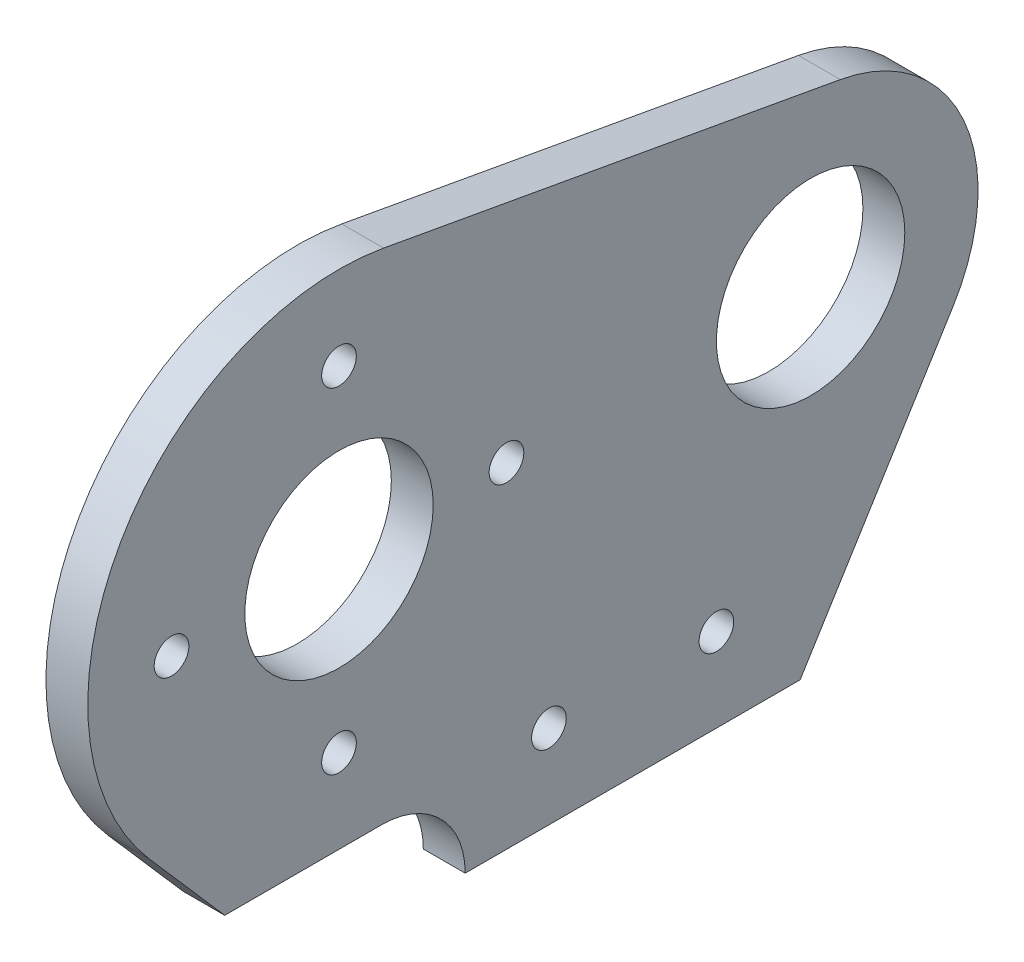
SolidWorks part; units mm, degrees
material "6061-T6 (SS)"
ref_plane "Front Plane" through (0, 0, 0) normal (0, 0, 1) x (1, 0, 0)
ref_plane "Top Plane" through (0, 0, 0) normal (0, 1, 0) x (1, 0, 0)
ref_plane "Right Plane" through (0, 0, 0) normal (1, 0, 0) x (0, 0, -1)
sketch "Sketch1" plane through (0, 0, 0) normal (1, 0, 0) x (0, 0, -1)
  line L0 (25.4, 12.7) -> (38.1, 12.7) construction
  line L1 (0, 0) -> (76.2, 0)
  line L5 (38.1, 12.7) -> (63.5, 12.7) construction
  line L6 (63.5, 12.7) -> (77.7875, 12.7) construction
  line L7 (77.7875, 12.7) -> (77.7875, 50.8) construction
  line L8 (77.7875, 50.8) -> (17.2031, 50.8) construction
  line L9 (76.2, 0) -> (99.3809, 37.4252)
  line L12 (6.2611, 50.8) -> (6.2611, 76.2) construction
  line L13 (0, 0) -> (-22.459, 25.7648)
  line L15 (38.1, 12.7) -> (38.1, 39.0177) construction
  line L18 (6.2611, 50.8) -> (6.2611, 25.4) construction
  line L19 (6.2611, 50.8) -> (31.6611, 50.8) construction
  line L20 (6.2611, 50.8) -> (-19.1389, 50.8) construction
  line L21 (82.2974, 75.7964) -> (13.026, 88.2946)
  line L22 (77.7875, 50.8) -> (6.2611, 50.8) construction
  circle A0 centre (38.1, 12.7) radius 2.6289
  circle A1 centre (63.5, 12.7) radius 2.6289
  circle A2 centre (77.7875, 50.8) radius 14.2875
  arc A3 (99.3809, 37.4252) -> (82.2974, 75.7964) centre (77.7875, 50.8) ccw
  circle A4 centre (6.2611, 50.8) radius 14.2875
  circle A5 centre (6.2611, 76.2) radius 2.6289
  arc A9 (13.026, 88.2946) -> (-22.459, 25.7648) centre (6.2611, 50.8) ccw
  circle A10 centre (6.2611, 25.4) radius 2.6289
  circle A11 centre (31.6611, 50.8) radius 2.6289
  circle A12 centre (-19.1389, 50.8) radius 2.6289
  dimension "D5" = 5.2578
  dimension "D6" = 5.2578
  dimension "D9" = 28.575
  dimension "D10" = 50.8
  dimension "D11" = 28.575
  dimension "D13" = 5.2578
  dimension "D15" = 76.2
  dimension "D17" = 5.2578
  dimension "D19" = 5.2578
  dimension "D21" = 5.2578
  dimension "D2" = 76.2
  dimension "D3" = 12.7
  dimension "D4" = 25.4
  dimension "D7" = 14.2875
  dimension "D8" = 38.1
  dimension "D12" = 25.4
  dimension "D16" = 71.5264
  dimension "D14" = 25.4
  dimension "D18" = 25.4
  dimension "D20" = 25.4
  dimension "D22" = 12.7
  dimension "D23" = 12.7
extrude "Boss-Extrude1" add sketch "Sketch1" along normal blind 6.35
sketch "Sketch2" plane through (0, 0, 0) normal (-1, 0, 0) x (0, 0, 1)
  line L1 (0, 0) -> (-25.4, 0)
  line L3 (0, 12.7) -> (-25.4, 12.7)
  line L4 (-25.4, 0) -> (-25.4, 12.7)
  line L5 (0, 12.7) -> (50.8, 12.7)
  line L7 (0, 0) -> (50.8, 0)
  line L8 (50.8, 12.7) -> (50.8, 0)
  dimension "D1" = 25.4
  dimension "D2" = 12.7
  dimension "D3" = 50.8
extrude "Cut-Extrude1" cut sketch "Sketch2" against normal blind 6.35
fillet "Fillet7" radius 12.7 1 edges at (3.175, 12.7, -25.4)
